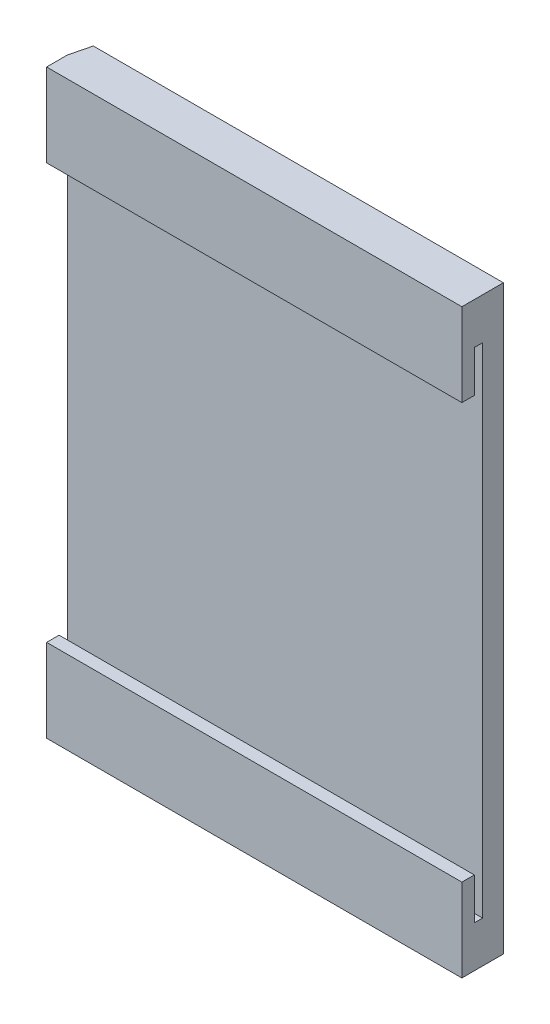
SolidWorks part; units mm, degrees
ref_plane "Front Plane" through (0, 0, 0) normal (0, 0, 1) x (1, 0, 0)
ref_plane "Top Plane" through (0, 0, 0) normal (0, 1, 0) x (1, 0, 0)
ref_plane "Right Plane" through (0, 0, 0) normal (1, 0, 0) x (0, 0, -1)
sketch "Sketch1" plane through (0, 0, 0) normal (0, 0, 1) x (1, 0, 0)
  line L0 (0, 60) -> (100, 60)
  line L1 (0, 70) -> (100, 70)
  line L2 (0, 70) -> (0, -70)
  line L3 (0, -70) -> (100, -70)
  line L4 (100, 70) -> (100, -70)
  line L5 (0, 50) -> (100, 50)
  line L6 (0, -60) -> (100, -60)
  line L7 (0, -50) -> (100, -50)
  line L8 (0, 0) -> (100, 0) construction
  line L9 (0, 0) -> (100, 0) construction
  point P15 (0, 0)
  dimension "D1" = 140
  dimension "D3" = 20
  dimension "D4" = 10
  dimension "D5" = 20
  dimension "D6" = 10
extrude "Boss-Extrude1" add sketch "Sketch1" along normal blind 5 and the other way blind 5 contours L2 L5 L4 L0 | L4 L1 L2 L0 | L7 L2 L6 L4 | L6 L2 L3 L4 | L2 L7 L4 L5 | L2 L1 L4 L3 region at (50, 65, 0) region at (50, 55, 0) region at (50, 0, 0) region at (50, -55, 0) region at (50, -65, 0)
extrude "Cut-Extrude1" cut sketch "Sketch1<3>" along normal through all contours L2 L7 L4 L5 | L2 L9 L4 L5 region at (50, 25, 0) region at (50, -25, 0)
sketch "Sketch1<3>" plane through (0, 0, 0) normal (0, 0, 1) x (1, 0, 0) same geometry as "Sketch1"
extrude "Cut-Extrude2" cut sketch "Sketch1<4>" along normal blind 2 contours L2 L5 L4 L0 | L7 L2 L6 L4 region at (50, 55, 0) region at (50, -55, 0)
sketch "Sketch1<4>" plane through (0, 0, 0) normal (0, 0, 1) x (1, 0, 0) same geometry as "Sketch1"
sketch "Sketch2" plane through (0, 0, 0) normal (0, 1, 0) x (1, 0, 0)
  line L0 (0, 0) -> (7.5, 30)
  line L3 (7.5, 30) -> (0, 30)
  line L5 (0, 30) -> (0, 0)
  point P0 (0, 0)
  dimension "D1" = 7.5
  dimension "D2" = 30
  dimension "D3" = 5
extrude "Cut-Extrude3" cut sketch "Sketch2" against normal through all both and the other way through all
